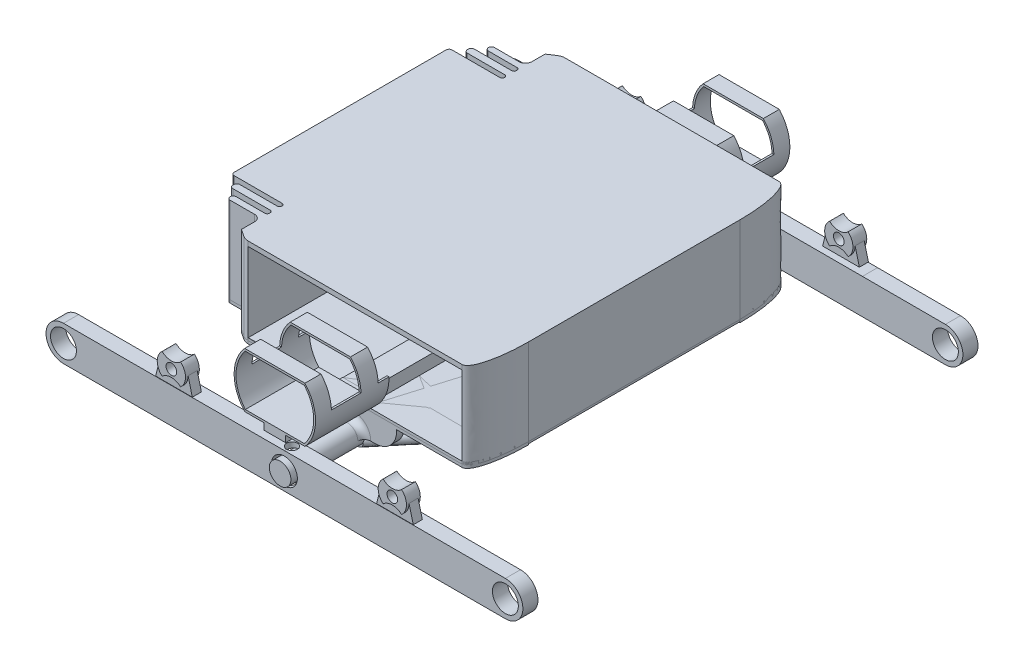
SolidWorks part; units mm, degrees
note: The reader was unsure of these and kept them because the rebuilt part matched: shared geometry of "Esquisse15<3>".
ref_plane "Plan de face" through (0, 0, 0) normal (0, 0, 1) x (1, 0, 0)
ref_plane "Plan de dessus" through (0, 0, 0) normal (0, 1, 0) x (1, 0, 0)
ref_plane "Plan de droite" through (0, 0, 0) normal (1, 0, 0) x (0, 0, -1)
sketch "Esquisse2" plane through (0, 0, 0) normal (0, 0, 1) x (1, 0, 0)
  line L0 (0, 0) -> (10.2363, 0) construction
  line L1 (10.2363, 0) -> (10.2363, 1.0347) construction
  line L2 (0, 0) -> (0, 3.2597) construction
  line L3 (-10.2363, 0) -> (10.2363, 0)
  line L4 (10.2363, 0) -> (10.2363, 1.0347) construction
  line L5 (10.2363, 1.6197) -> (0, 1.6298)
  line L6 (10.2363, 1.6197) -> (10.2363, 10.3085) construction
  line L7 (-10.2363, 1.6197) -> (0, 1.6298)
  arc A0 (10.2363, 0) -> (10.2363, 1.6197) centre (10.2363, 0.8098) ccw
  arc A1 (-10.2363, 0) -> (-10.2363, 1.6197) centre (-10.2363, 0.8098) cw
  circle A2 centre (-10.2363, 0.8098) radius 0.6
  circle A3 centre (10.2363, 0.8098) radius 0.6
  circle A4 centre (0, 0.8098) radius 0.6
  point P11 (0, 1.0347)
extrude "Boss.-Extru.1" add sketch "Esquisse2" along normal blind 0.7
sketch "Esquisse3" plane through (0, 0, 0) normal (0, 0, -1) x (-1, 0, 0)
  circle A0 centre (0, 0.8098) radius 0.5
extrude "Boss.-Extru.2" add sketch "Esquisse3" along normal blind 2.5 and the other way blind 0.9 separate body
sketch "Esquisse4" plane through (0, 0, -2.5) normal (0, 0, -1) x (-1, 0, 0)
  line L0 (0, 1.8685) -> (0, 2.6207) construction
  line L1 (-1.0004, 0.8098) -> (1.0004, 0.8098)
  line L2 (-2.0004, 1.8685) -> (-2.0004, 1.8098)
  line L3 (-2.0004, 1.8685) -> (2.0004, 1.8685)
  line L4 (2.0004, 1.8098) -> (2.0004, 1.8685)
  arc A0 (2.0004, 1.8098) -> (1.0004, 0.8098) centre (1.0004, 1.8098) cw
  arc A1 (-2.0004, 1.8098) -> (-1.0004, 0.8098) centre (-1.0004, 1.8098) ccw
  dimension "D1" = 1
extrude "Boss.-Extru.3" add sketch "Esquisse4" along normal blind 0.35
sketch "Esquisse5" plane through (0, 1.8685, 0) normal (0, 1, 0) x (1, 0, 0)
  line L1 (-4.8814, 2.5) -> (5.0307, 2.5)
  line L2 (5.0307, 4.9426) -> (5.6618, 4.9426)
  line L3 (-5.0307, 4.9426) -> (5.0307, 4.9426)
  line L4 (-5.1556, 2.5818) -> (-5.5015, 2.8086)
  line L6 (-5.5015, 2.8086) -> (-5.5015, 3.4186)
  line L7 (-5.8015, 3.7186) -> (-6.9343, 3.7186)
  line L8 (-7.0743, 3.8586) -> (-7.0743, 3.8595)
  line L9 (-6.9343, 3.9995) -> (-5.6015, 3.9995)
  line L10 (-5.5015, 4.0995) -> (-5.5015, 4.1466)
  line L11 (-5.6015, 4.2466) -> (-7.3388, 4.2466)
  line L12 (-7.4788, 4.3866) -> (-7.4788, 4.4324)
  line L13 (-7.3388, 4.5724) -> (-5.6015, 4.5724)
  line L14 (-5.5015, 4.6724) -> (-5.5015, 4.6971)
  line L15 (-5.6015, 4.7971) -> (-7.8219, 4.7971)
  line L16 (-7.9619, 4.9371) -> (-7.9619, 4.9426)
  line L17 (-7.9619, 4.9426) -> (-5.0307, 4.9426)
  arc A0 (-4.8814, 2.5) -> (-5.1556, 2.5818) centre (-4.8814, 3) cw
  arc A1 (-5.5015, 3.4186) -> (-5.8015, 3.7186) centre (-5.8015, 3.4186) ccw
  arc A2 (-5.5015, 4.0995) -> (-5.6015, 3.9995) centre (-5.6015, 4.0995) cw
  arc A3 (-5.5015, 4.1466) -> (-5.6015, 4.2466) centre (-5.6015, 4.1466) ccw
  arc A4 (-5.5015, 4.6724) -> (-5.6015, 4.5724) centre (-5.6015, 4.6724) cw
  arc A5 (-5.5015, 4.6971) -> (-5.6015, 4.7971) centre (-5.6015, 4.6971) ccw
  arc A6 (-6.9343, 3.9995) -> (-7.0743, 3.8595) centre (-6.9343, 3.8595) ccw
  arc A7 (-7.0743, 3.8586) -> (-6.9343, 3.7186) centre (-6.9343, 3.8586) ccw
  arc A8 (-7.4788, 4.3866) -> (-7.3388, 4.2466) centre (-7.3388, 4.3866) ccw
  arc A9 (-7.3388, 4.5724) -> (-7.4788, 4.4324) centre (-7.3388, 4.4324) ccw
  arc A10 (-7.9619, 4.9371) -> (-7.8219, 4.7971) centre (-7.8219, 4.9371) ccw
  circle A11 centre (4.3996, 4.2466) radius 0.4408
  circle A12 centre (1.9237, 4.2466) radius 0.4249
  circle A13 centre (-0.5711, 4.2466) radius 0.4149
  ellipse E0 centre (5.0307, 4.9426) end of major axis (5.0307, 2.5) minor radius 0.6311 (5.0307, 2.5) -> (5.6618, 4.9426) ccw
  dimension "D1" = 0.5
  dimension "D2" = 0.3
  dimension "D3" = 0.1
  dimension "D4" = 0.1
  dimension "D5" = 0.1
  dimension "D6" = 0.1
  dimension "D7" = 0.14
  dimension "D8" = 0.14
  dimension "D9" = 0.14
  dimension "D10" = 0.14
extrude "Boss.-Extru.4" add sketch "Esquisse5" along normal blind 0.25
sketch "Esquisse6" plane through (0, 0, -4.9426) normal (0, 0, -1) x (-1, 0, 0)
  line L0 (7.9619, 2.1145) -> (7.9619, 1.9158)
  line L1 (-5.6618, 1.9119) -> (-5.6618, 2.1184)
  ellipse E0 centre (1.1403, 2.0152) end of major axis (8.199, 2.0152) minor radius 0.3865 (7.9619, 2.1145) -> (-5.6618, 2.1184) ccw
  ellipse E1 centre (1.1403, 2.0152) end of major axis (8.199, 2.0152) minor radius 0.3865 (-5.6618, 1.9119) -> (7.9619, 1.9158) ccw
extrude "Boss.-Extru.5" add sketch "Esquisse6" along normal blind 4.9
mirror "Symétrie2" about plane through (-1.1403, 2.0152, -9.8426) normal (0, 0, -1) of bodies 101 107
sketch "Esquisse7" plane through (5.6618, 0, 0) normal (1, 0, 0) x (0, 0, -1)
  line L0 (9.8426, 2.4016) -> (9.8426, 3.9628) construction
  line L1 (5.5715, 2.6871) -> (5.5715, 2.265)
  line L2 (5.5715, 2.6871) -> (14.1138, 2.6871)
  line L4 (5.5715, 2.265) -> (14.1138, 2.265)
  line L5 (14.1138, 2.6871) -> (14.1138, 2.265)
extrude "Enlèv. mat.-Extru.1" cut sketch "Esquisse7" against normal blind 14.9
sketch "Esquisse8" plane through (-0.0016, 1.6298, 0) normal (-0.001, 1, 0) x (1, 0.001, 0)
  line L0 (0.0016, -0.7) -> (0.0016, 0) construction
  line L1 (0.0016, 20.3852) -> (0.0016, 19.6852) construction
  circle A0 centre (0.0016, -0.35) radius 0.25
  circle A1 centre (0.0016, 20.0352) radius 0.25
extrude "Enlèv. mat.-Extru.2" cut sketch "Esquisse8" against normal blind 8.9
fillet "Congé5" radius 0.3 1 edges at (0, 1.3098, -2.5)
fillet "Congé6" radius 0.3 1 edges at (0, 1.3098, -17.1852)
sketch "Esquisse9" plane through (0, 2.1185, 0) normal (0, 1, 0) x (1, 0, 0)
  line L0 (-0.5, 2.7366) -> (0.5, 2.7366)
  line L2 (-0.5, 2.7366) -> (-0.5, 3.728)
  line L3 (-0.5, 3.728) -> (0.5, 3.728)
  line L4 (0.5, 2.7366) -> (0.5, 3.728)
  line L5 (0.5, 16.9486) -> (0.5, 15.9573)
  line L6 (-0.5, 15.9573) -> (0.5, 15.9573)
  line L7 (-0.5, 16.9486) -> (-0.5, 15.9573)
  line L8 (-0.5, 16.9486) -> (0.5, 16.9486)
extrude "Boss.-Extru.6" add sketch "Esquisse9" along normal blind 3.3
sketch "Esquisse10" plane through (0, 5.4185, 0) normal (0, 1, 0) x (1, 0, 0)
  line L0 (-7.9619, 9.8426) -> (7.2604, 9.8426) construction
  line L1 (-0.5, 3.728) -> (0.5, 3.728)
  line L2 (-0.5, 3.728) -> (-0.5, -1.1448)
  line L3 (-0.5, -1.1448) -> (0.5, -1.1448)
  line L4 (0.5, 3.728) -> (0.5, -1.1448)
  line L5 (-7.9619, 14.7426) -> (-7.9619, 4.9426) construction
  line L6 (-0.5, 20.83) -> (0.5, 20.83)
  line L7 (-0.5, 15.9573) -> (0.5, 15.9573)
  line L8 (0.5, 15.9573) -> (0.5, 20.83)
  line L9 (-0.5, 15.9573) -> (-0.5, 20.83)
extrude "Boss.-Extru.7" add sketch "Esquisse10" along normal blind 0.3
fillet "Congé7" radius 0.65 2 edges at (0, 5.7185, -15.9573) (0, 5.7185, -3.728)
sketch "Esquisse11" plane through (0, 0, 1.1448) normal (0, 0, 1) x (1, 0, 0)
  line L0 (-1.2775, 5.7185) -> (1.2775, 5.7185)
  line L1 (-0.5, 5.7185) -> (0.5, 5.7185) construction
  line L2 (0, 6.9866) -> (0, 6.1918) construction
  line L3 (0, 5.7185) -> (1.2775, 5.7185)
  line L4 (1.2775, 5.7185) -> (1.396, 5.7185)
  line L5 (-1.3679, 5.8166) -> (1.3679, 5.8166)
  line L6 (0, 6.9866) -> (0.9813, 6.9866) construction
  line L7 (-1.2775, 5.7185) -> (-1.396, 5.7185)
  line L8 (-1.2775, 8.2546) -> (1.2775, 8.2546)
  line L9 (-1.3679, 8.1566) -> (1.3679, 8.1566)
  line L10 (-1.2775, 8.2546) -> (-1.396, 8.2546)
  line L11 (1.2775, 8.2546) -> (1.396, 8.2546)
  arc A0 (1.3679, 5.8166) -> (1.3679, 8.1566) centre (0, 6.9866) ccw
  arc A1 (1.396, 5.7185) -> (1.396, 8.2546) centre (0, 6.9866) ccw
  arc A2 (-1.3679, 8.1566) -> (-1.3679, 5.8166) centre (0, 6.9866) ccw
  arc A3 (-1.396, 8.2546) -> (-1.396, 5.7185) centre (0, 6.9866) ccw
  line M3 (0.5, 5.7185) -> (-0.5, 5.7185)
  dimension "D1" = 1.17
extrude "Boss.-Extru.8" add sketch "Esquisse11" against normal blind 3.4 contours L10 A3 L7 L0 L4 A1 L11 L8 A2 L9 A0 L5 M3
sketch "Esquisse12" plane through (0, 8.2546, 0) normal (0, 1, 0) x (1, 0, 0)
  line L1 (-2.4978, 2.8381) -> (2.5755, 2.8381)
  line L2 (-2.4978, 2.8381) -> (-2.4978, 1.7564)
  line L3 (-2.4978, 1.7564) -> (2.5755, 1.7564)
  line L4 (2.5755, 2.8381) -> (2.5755, 1.7564)
  line L5 (-2.4978, 0.9642) -> (2.5755, 0.9642)
  line L6 (-2.4978, 0.9642) -> (-2.4978, -0.407)
  line L7 (-2.4978, -0.407) -> (2.5755, -0.407)
  line L8 (2.5755, 0.9642) -> (2.5755, -0.407)
extrude "Enlèv. mat.-Extru.3" cut sketch "Esquisse12" against normal blind 1.2
ref_plane "Plan1" through (0, 0, -9.8426) normal (0, 0, 1) x (1, 0, 0)
mirror "Symétrie3" about plane through (0, 0, -9.8426) normal (0, 0, 1) of "Enlèv. mat.-Extru.3", "Boss.-Extru.8"
sketch "Esquisse13" plane through (0, 0, -16.9486) normal (0, 0, -1) x (-1, 0, 0)
  line L1 (-0.7148, 5.4185) -> (0.5725, 5.4185)
  line L2 (-0.7148, 5.4185) -> (-0.7148, 2.4358)
  line L3 (-0.7148, 2.4358) -> (0.5725, 2.4358)
  line L4 (0.5725, 5.4185) -> (0.5725, 2.4358)
extrude "Enlèv. mat.-Extru.4" cut sketch "Esquisse13" against normal blind 15
pattern_linear "Répétition linéaire1" count 2 spacing 3 along (0, -1, 0) of bodies 122 123
sketch "Esquisse14" plane through (0, 0, 1.1448) normal (0, 0, 1) x (1, 0, 0)
  line L1 (-2.4627, 8.6462) -> (2.6532, 8.6462)
  line L2 (-2.4627, 8.6462) -> (-2.4627, 5.3359)
  line L3 (-2.4627, 5.3359) -> (2.6532, 5.3359)
  line L4 (2.6532, 8.6462) -> (2.6532, 5.3359)
extrude "Enlèv. mat.-Extru.5" cut sketch "Esquisse14" against normal blind 23
sketch "Esquisse15" plane through (0, 0, -20.3852) normal (0, 0, -1) x (-1, 0, 0)
  line L0 (0, 0.8098) -> (0, 7.5747) construction
  line L1 (5.7737, 2.3982) -> (5.9728, 1.6239)
  line L2 (0, 1.6298) -> (10.2363, 1.6197) construction
  line L3 (5.3656, 2.3982) -> (6.0808, 2.3982) construction
  line L4 (5.1182, 2.6456) -> (5.1182, 3.4486) construction
  line L5 (4.4626, 2.3982) -> (4.2635, 1.6239)
  line L6 (4.2635, 1.6239) -> (5.9728, 1.6239)
  line L7 (-5.1182, 2.6456) -> (-5.1182, 3.4486) construction
  line L8 (-5.3656, 2.3982) -> (-6.0808, 2.3982) construction
  line L9 (-4.2635, 1.6239) -> (-5.9728, 1.6239)
  line L10 (-4.4626, 2.3982) -> (-4.2635, 1.6239)
  line L11 (-5.7737, 2.3982) -> (-5.9728, 1.6239)
  arc A0 (5.5451, 1.9007) -> (5.5451, 2.8957) centre (5.1182, 2.3982) ccw
  circle A1 centre (5.1182, 2.3982) radius 0.2474
  arc A2 (5.5451, 1.9007) -> (4.6912, 1.9007) centre (5.1182, 1.4347) ccw
  arc A3 (5.5451, 2.8957) -> (4.6912, 2.8957) centre (5.1182, 3.3617) cw
  arc A4 (4.6912, 2.8957) -> (4.6912, 1.9007) centre (5.1182, 2.3982) ccw
  arc A5 (-4.6912, 2.8957) -> (-4.6912, 1.9007) centre (-5.1182, 2.3982) cw
  arc A6 (-5.5451, 2.8957) -> (-4.6912, 2.8957) centre (-5.1182, 3.3617) ccw
  arc A7 (-5.5451, 1.9007) -> (-4.6912, 1.9007) centre (-5.1182, 1.4347) cw
  circle A8 centre (-5.1182, 2.3982) radius 0.2474
  arc A9 (-5.5451, 1.9007) -> (-5.5451, 2.8957) centre (-5.1182, 2.3982) cw
  line M5 (10.2363, 1.6197) -> (0, 1.6298)
  line M6 (0, 1.6298) -> (-10.2363, 1.6197)
extrude "Boss.-Extru.9" add sketch "Esquisse15" against normal blind 0.42 contours A7 A9 L11 L10 A5 M6 | A4 L5 L1 A0 A2 M5
extrude "Boss.-Extru.10" add sketch "Esquisse15<3>" along normal blind 0.12 and the other way blind 0.52 contours A9 A7 A5 A6 A8 | A3 A4 A2 A0 A1
sketch "Esquisse15<3>" plane through (0, 0, -20.3852) normal (0, 0, -1) x (-1, 0, 0) same geometry as "Esquisse15"
sketch "Esquisse16" plane through (0, 0, -20.3852) normal (0, 0, -1) x (-1, 0, 0)
  line L0 (-10.2363, 1.6197) -> (-5.9728, 1.6239) construction
  line L1 (-6.3931, 1.6235) -> (6.2627, 1.6235)
  line L2 (-6.3931, 1.6235) -> (-6.3931, 1.6388)
  line L3 (-6.3931, 1.6388) -> (6.2627, 1.6388)
  line L4 (6.2627, 1.6235) -> (6.2627, 1.6388)
extrude "Enlèv. mat.-Extru.6" cut sketch "Esquisse16" against normal blind 0.82
mirror "Symétrie5" about plane through (0, 0, -9.8426) normal (0, 0, 1) of bodies 130 131
ref_plane "Plan2" through (0, -8.1275, -9.6859) normal (0, -0.6428, -0.766) x (1, 0, 0)
ref_plane "Plan3" through (-8.639, 0, -7.249) normal (-0.766, 0, -0.6428) x (-0.6428, 0, 0.766)
sketch "Esquisse19" plane through (-8.639, 0, -7.249) normal (-0.766, 0, -0.6428) x (-0.6428, 0, 0.766)
  line L0 (-13.2066, 0.4884) -> (-10.59, 0.4884)
  line L1 (-9.89, 1.1884) -> (-9.89, 1.633)
  arc A0 (-10.59, 0.4884) -> (-9.89, 1.1884) centre (-10.59, 1.1884) ccw
  ellipse E0 centre (-10.5605, 2.0152) end of major axis (-6.0233, 2.0152) minor radius 0.3865 (-14.7582, 1.8685) -> (-6.3628, 1.8685) ccw construction
  dimension "D1" = 0.7
sketch "Esquisse20" plane through (0, 0, -17.1852) normal (0, 0, -1) x (-1, 0, 0)
  circle A0 centre (0.2089, 0.536) radius 0.2366
sweep "Balayage1" add profiles "Esquisse20" path "Esquisse19"
ref_plane "Plan4" through (0, 0, 0) normal (1, 0, 0) x (0, 0, -1)
mirror "Symétrie6" about plane through (0, 0, 0) normal (1, 0, 0) of "Balayage1"
mirror "Symétrie7" about plane through (0, 0, -9.8426) normal (0, 0, 1) of "Symétrie6", "Balayage1"
ref_plane "Plane1" through (-6.5258, 2.265, -14.1138) normal (0, 0, -1) x (-1, 0, 0)
sketch "Sketch3" plane through (0, 0, 0) normal (0, 1, 0) x (1, 0, 0)
  line L0 (5.6618, 4.9426) -> (5.6618, 14.7426) construction
  line L1 (5.6615, 14.7426) -> (5.6618, 14.7426) construction
  line L2 (5.6615, 14.7426) -> (-7.9421, 14.7426) construction
  line L3 (-7.9619, 14.7426) -> (-7.9421, 14.7426) construction
  line L4 (-7.9619, 14.7426) -> (-7.9619, 4.9426) construction
  line L5 (-7.9421, 4.9426) -> (-7.9619, 4.9426) construction
  line L6 (-7.9421, 4.9426) -> (5.6615, 4.9426) construction
  line L7 (5.6618, 4.9426) -> (5.6615, 4.9426) construction
  line L8 (-5.1556, 17.1034) -> (-5.5015, 16.8766) construction
  line L9 (-5.5015, 16.8766) -> (-5.5015, 16.2666) construction
  line L10 (-5.8015, 15.9666) -> (-6.9343, 15.9666) construction
  line L11 (-7.0743, 15.8266) -> (-7.0743, 15.8258) construction
  line L12 (-6.9343, 15.6858) -> (-5.6015, 15.6858) construction
  line L13 (-5.5015, 15.5858) -> (-5.5015, 15.5386) construction
  line L14 (-5.6015, 15.4386) -> (-7.3388, 15.4386) construction
  line L15 (-7.4788, 15.2986) -> (-7.4788, 15.2528) construction
  line L16 (-7.3388, 15.1128) -> (-5.6015, 15.1128) construction
  line L17 (-5.5015, 15.0128) -> (-5.5015, 14.9881) construction
  line L18 (-5.6015, 14.8881) -> (-7.8219, 14.8881) construction
  line L19 (-7.9619, 14.7481) -> (-7.9619, 14.7426) construction
  line L20 (-7.9619, 14.7426) -> (-7.9421, 14.7426) construction
  line L21 (-7.9421, 14.7426) -> (5.6615, 14.7426) construction
  line L22 (5.6615, 14.7426) -> (5.6618, 14.7426) construction
  line L23 (5.0307, 17.1852) -> (-4.8814, 17.1852) construction
  line L24 (-5.5015, 16.8766) -> (-5.1556, 17.1034) construction
  line L25 (5.6618, 4.9426) -> (5.6618, 14.7426)
  line L26 (5.6615, 14.7426) -> (5.6618, 14.7426)
  line L27 (5.6615, 14.7426) -> (-7.9421, 14.7426)
  line L28 (-7.9619, 14.7426) -> (-7.9421, 14.7426)
  line L29 (-7.9619, 14.7426) -> (-7.9619, 4.9426)
  line L30 (-7.9421, 4.9426) -> (-7.9619, 4.9426)
  line L31 (-7.9421, 4.9426) -> (5.6615, 4.9426)
  line L32 (5.6618, 4.9426) -> (5.6615, 4.9426)
  line L33 (-5.1556, 17.1034) -> (-5.5015, 16.8766)
  line L34 (-5.5015, 16.8766) -> (-5.5015, 16.2666)
  line L35 (-5.8015, 15.9666) -> (-6.9343, 15.9666)
  line L36 (-7.0743, 15.8266) -> (-7.0743, 15.8258)
  line L37 (-6.9343, 15.6858) -> (-5.6015, 15.6858)
  line L38 (-5.5015, 15.5858) -> (-5.5015, 15.5386)
  line L39 (-5.6015, 15.4386) -> (-7.3388, 15.4386)
  line L40 (-7.4788, 15.2986) -> (-7.4788, 15.2528)
  line L41 (-7.3388, 15.1128) -> (-5.6015, 15.1128)
  line L42 (-5.5015, 15.0128) -> (-5.5015, 14.9881)
  line L43 (-5.6015, 14.8881) -> (-7.8219, 14.8881)
  line L44 (-7.9619, 14.7481) -> (-7.9619, 14.7426)
  line L45 (-7.9619, 14.7426) -> (-7.9421, 14.7426)
  line L46 (-7.9421, 14.7426) -> (5.6615, 14.7426)
  line L47 (5.6615, 14.7426) -> (5.6618, 14.7426)
  line L48 (5.0307, 17.1852) -> (-4.8814, 17.1852)
  line L49 (-5.5015, 16.8766) -> (-5.1556, 17.1034)
  line L66 (-4.8814, 2.5) -> (5.0307, 2.5)
  line L67 (5.6618, 4.9426) -> (5.6615, 4.9426)
  line L68 (5.6615, 4.9426) -> (-7.9421, 4.9426)
  line L69 (-7.9421, 4.9426) -> (-7.9619, 4.9426)
  line L70 (-7.9619, 4.9426) -> (-7.9619, 4.9371)
  line L71 (-7.8219, 4.7971) -> (-5.6015, 4.7971)
  line L72 (-5.5015, 4.6971) -> (-5.5015, 4.6724)
  line L73 (-5.6015, 4.5724) -> (-7.3388, 4.5724)
  line L74 (-7.4788, 4.4324) -> (-7.4788, 4.3866)
  line L75 (-7.3388, 4.2466) -> (-5.6015, 4.2466)
  line L76 (-5.5015, 4.1466) -> (-5.5015, 4.0995)
  line L77 (-5.6015, 3.9995) -> (-6.9343, 3.9995)
  line L78 (-7.0743, 3.8595) -> (-7.0743, 3.8586)
  line L79 (-6.9343, 3.7186) -> (-5.8015, 3.7186)
  line L80 (-5.5015, 3.4186) -> (-5.5015, 2.8086)
  line L81 (-5.5015, 2.8086) -> (-5.1556, 2.5818)
  line L82 (-4.8814, 2.5) -> (5.0307, 2.5)
  line L83 (5.6618, 4.9426) -> (5.6615, 4.9426)
  line L84 (5.6615, 4.9426) -> (-7.9421, 4.9426)
  line L85 (-7.9421, 4.9426) -> (-7.9619, 4.9426)
  line L86 (-7.9619, 4.9426) -> (-7.9619, 4.9371)
  line L87 (-7.8219, 4.7971) -> (-5.6015, 4.7971)
  line L88 (-5.5015, 4.6971) -> (-5.5015, 4.6724)
  line L89 (-5.6015, 4.5724) -> (-7.3388, 4.5724)
  line L90 (-7.4788, 4.4324) -> (-7.4788, 4.3866)
  line L91 (-7.3388, 4.2466) -> (-5.6015, 4.2466)
  line L92 (-5.5015, 4.1466) -> (-5.5015, 4.0995)
  line L93 (-5.6015, 3.9995) -> (-6.9343, 3.9995)
  line L94 (-7.0743, 3.8595) -> (-7.0743, 3.8586)
  line L95 (-6.9343, 3.7186) -> (-5.8015, 3.7186)
  line L96 (-5.5015, 3.4186) -> (-5.5015, 2.8086)
  line L97 (-5.5015, 2.8086) -> (-5.1556, 2.5818)
  arc A0 (-4.8814, 17.1852) -> (-5.1556, 17.1034) centre (-4.8814, 16.6852) ccw construction
  arc A1 (-5.8015, 15.9666) -> (-5.5015, 16.2666) centre (-5.8015, 16.2666) ccw construction
  arc A2 (-6.9343, 15.9666) -> (-7.0743, 15.8266) centre (-6.9343, 15.8266) ccw construction
  arc A3 (-7.0743, 15.8258) -> (-6.9343, 15.6858) centre (-6.9343, 15.8258) ccw construction
  arc A4 (-5.5015, 15.5858) -> (-5.6015, 15.6858) centre (-5.6015, 15.5858) ccw construction
  arc A5 (-5.6015, 15.4386) -> (-5.5015, 15.5386) centre (-5.6015, 15.5386) ccw construction
  arc A6 (-7.3388, 15.4386) -> (-7.4788, 15.2986) centre (-7.3388, 15.2986) ccw construction
  arc A7 (-7.4788, 15.2528) -> (-7.3388, 15.1128) centre (-7.3388, 15.2528) ccw construction
  arc A8 (-5.5015, 15.0128) -> (-5.6015, 15.1128) centre (-5.6015, 15.0128) ccw construction
  arc A9 (-5.6015, 14.8881) -> (-5.5015, 14.9881) centre (-5.6015, 14.9881) ccw construction
  arc A10 (-7.8219, 14.8881) -> (-7.9619, 14.7481) centre (-7.8219, 14.7481) ccw construction
  arc A11 (-4.8814, 17.1852) -> (-5.1556, 17.1034) centre (-4.8814, 16.6852) ccw
  arc A12 (-5.8015, 15.9666) -> (-5.5015, 16.2666) centre (-5.8015, 16.2666) ccw
  arc A13 (-6.9343, 15.9666) -> (-7.0743, 15.8266) centre (-6.9343, 15.8266) ccw
  arc A14 (-7.0743, 15.8258) -> (-6.9343, 15.6858) centre (-6.9343, 15.8258) ccw
  arc A15 (-5.5015, 15.5858) -> (-5.6015, 15.6858) centre (-5.6015, 15.5858) ccw
  arc A16 (-5.6015, 15.4386) -> (-5.5015, 15.5386) centre (-5.6015, 15.5386) ccw
  arc A17 (-7.3388, 15.4386) -> (-7.4788, 15.2986) centre (-7.3388, 15.2986) ccw
  arc A18 (-7.4788, 15.2528) -> (-7.3388, 15.1128) centre (-7.3388, 15.2528) ccw
  arc A19 (-5.5015, 15.0128) -> (-5.6015, 15.1128) centre (-5.6015, 15.0128) ccw
  arc A20 (-5.6015, 14.8881) -> (-5.5015, 14.9881) centre (-5.6015, 14.9881) ccw
  arc A21 (-7.8219, 14.8881) -> (-7.9619, 14.7481) centre (-7.8219, 14.7481) ccw
  arc A33 (-5.1556, 2.5818) -> (-4.8814, 2.5) centre (-4.8814, 3) ccw
  arc A34 (-7.9619, 4.9371) -> (-7.8219, 4.7971) centre (-7.8219, 4.9371) ccw
  arc A35 (-5.5015, 4.6971) -> (-5.6015, 4.7971) centre (-5.6015, 4.6971) ccw
  arc A36 (-5.6015, 4.5724) -> (-5.5015, 4.6724) centre (-5.6015, 4.6724) ccw
  arc A37 (-7.3388, 4.5724) -> (-7.4788, 4.4324) centre (-7.3388, 4.4324) ccw
  arc A38 (-7.4788, 4.3866) -> (-7.3388, 4.2466) centre (-7.3388, 4.3866) ccw
  arc A39 (-5.5015, 4.1466) -> (-5.6015, 4.2466) centre (-5.6015, 4.1466) ccw
  arc A40 (-5.6015, 3.9995) -> (-5.5015, 4.0995) centre (-5.6015, 4.0995) ccw
  arc A41 (-6.9343, 3.9995) -> (-7.0743, 3.8595) centre (-6.9343, 3.8595) ccw
  arc A42 (-7.0743, 3.8586) -> (-6.9343, 3.7186) centre (-6.9343, 3.8586) ccw
  arc A43 (-5.5015, 3.4186) -> (-5.8015, 3.7186) centre (-5.8015, 3.4186) ccw
  arc A44 (-5.1556, 2.5818) -> (-4.8814, 2.5) centre (-4.8814, 3) ccw
  arc A45 (-7.9619, 4.9371) -> (-7.8219, 4.7971) centre (-7.8219, 4.9371) ccw
  arc A46 (-5.5015, 4.6971) -> (-5.6015, 4.7971) centre (-5.6015, 4.6971) ccw
  arc A47 (-5.6015, 4.5724) -> (-5.5015, 4.6724) centre (-5.6015, 4.6724) ccw
  arc A48 (-7.3388, 4.5724) -> (-7.4788, 4.4324) centre (-7.3388, 4.4324) ccw
  arc A49 (-7.4788, 4.3866) -> (-7.3388, 4.2466) centre (-7.3388, 4.3866) ccw
  arc A50 (-5.5015, 4.1466) -> (-5.6015, 4.2466) centre (-5.6015, 4.1466) ccw
  arc A51 (-5.6015, 3.9995) -> (-5.5015, 4.0995) centre (-5.6015, 4.0995) ccw
  arc A52 (-6.9343, 3.9995) -> (-7.0743, 3.8595) centre (-6.9343, 3.8595) ccw
  arc A53 (-7.0743, 3.8586) -> (-6.9343, 3.7186) centre (-6.9343, 3.8586) ccw
  arc A54 (-5.5015, 3.4186) -> (-5.8015, 3.7186) centre (-5.8015, 3.4186) ccw
  ellipse E0 centre (5.0307, 14.7426) end of major axis (5.0307, 17.1852) minor radius 0.6311 (5.6618, 14.7426) -> (5.0307, 17.1852) ccw construction
  ellipse E1 centre (5.0307, 14.7426) end of major axis (5.0307, 17.1852) minor radius 0.6311 (5.6618, 14.7426) -> (5.0307, 17.1852) ccw
  ellipse E3 centre (5.0307, 4.9426) end of major axis (5.0307, 2.5) minor radius 0.6311 (5.0307, 2.5) -> (5.6618, 4.9426) ccw
  ellipse E4 centre (5.0307, 4.9426) end of major axis (5.0307, 2.5) minor radius 0.6311 (5.0307, 2.5) -> (5.6618, 4.9426) ccw
  dimension "D1" = 0
extrude "Boss-Extrude2" add sketch "Sketch3" along normal blind 4 from offset 2 separate body contours L32 L25 L26 L27 L28 L29 L30 L31 | L26 E1 L48 A11 L33 L34 A12 L35 A13 L36 A14 L37 A15 L38 A16 L39 A17 L40 A18 L41 A19 L42 A20 L43 A21 L44 L28 L27 | L82 E4 L32 L31 L30 L86 A45 L87 A46 L88 A47 L89 A48 L90 A49 L91 A50 L92 A51 L93 A52 L94 A53 L95 A54 L96 L97 A44
sketch "Sketch4" plane through (0, 0, -2.5) normal (0, 0, 1) x (1, 0, 0)
  line L4 (-4.8814, 5.7794) -> (5.0307, 5.7794)
  line L5 (-4.8814, 6) -> (-4.8814, 2) construction
  line L6 (5.0307, 6) -> (5.0307, 2) construction
  line L7 (5.0307, 5.7794) -> (5.0307, 2.1185)
  line L9 (0.6037, 2.1185) -> (0.6037, 2.7165)
  line L10 (0.6037, 2.7165) -> (-0.4905, 2.7165)
  line L12 (-0.4905, 2.7165) -> (-0.4905, 2.1185)
  line L13 (-4.8814, 2.1185) -> (5.0307, 2.1185) construction
  line L14 (-0.4905, 2.1185) -> (-4.8814, 2.1185)
  line L15 (-4.8814, 2.1185) -> (-4.8814, 5.7794)
  line L16 (0.6037, 2.1185) -> (5.0307, 2.1185)
extrude "Cut-Extrude1" cut sketch "Sketch4" against normal blind 14.8
